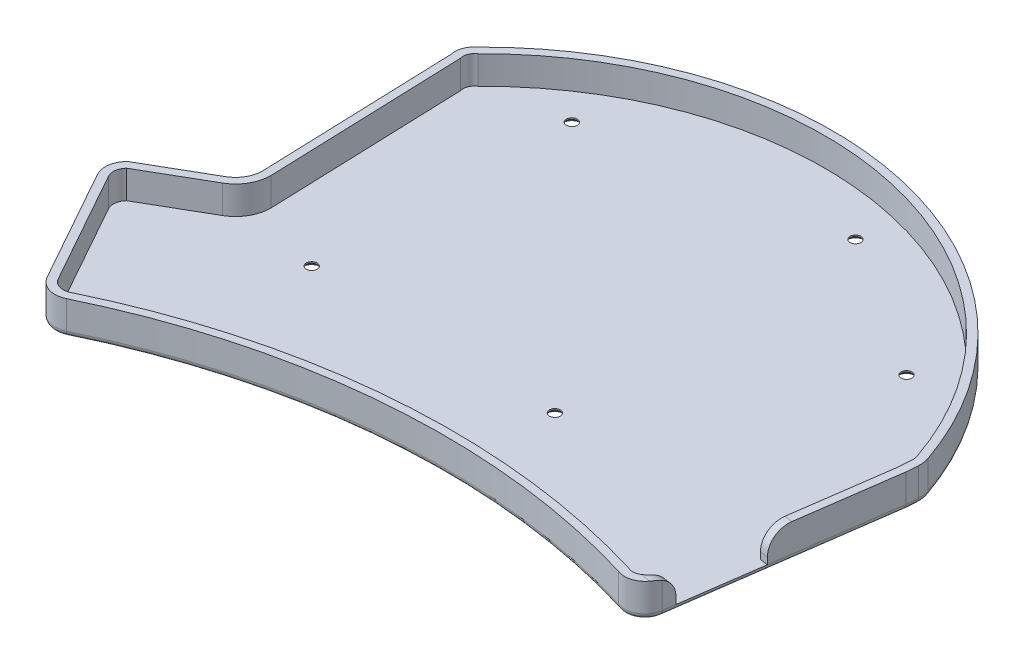
SolidWorks part; units mm, degrees
ref_plane "Front Plane" through (0, 0, 0) normal (0, 0, 1) x (1, 0, 0)
ref_plane "Top Plane" through (0, 0, 0) normal (0, 1, 0) x (1, 0, 0)
ref_plane "Right Plane" through (0, 0, 0) normal (1, 0, 0) x (0, 0, -1)
sketch "Sketch6" plane through (0, 1038.5381, 0) normal (0, 1, 0) x (1, 0, 0)
  line L0 (998.5428, -1001.8093) -> (999.7992, -1037.8748)
  line L1 (997.2992, -1042.205) -> (985.901, -1048.7857)
  line L2 (985.1163, -1053.683) -> (996.8887, -1074.7376)
  line L3 (1101.7127, -1066.0782) -> (1107.2534, -1026.654)
  line L4 (1107.2534, -1026.654) -> (1107.4097, -1024.4677)
  line L5 (1105.7609, -1026.4959) -> (1105.9135, -1024.3608)
  line L6 (1100.2273, -1065.8695) -> (1105.7609, -1026.4959)
  line L7 (986.4256, -1052.951) -> (998.198, -1074.0056)
  line L8 (998.0492, -1043.504) -> (986.8112, -1049.9922)
  line L9 (1000.0368, -1001.6089) -> (1001.2992, -1037.847)
  arc A0 (999.7992, -1037.8748) -> (997.2992, -1042.205) centre (994.7992, -1037.8748) cw
  arc A1 (985.901, -1048.7857) -> (985.1163, -1053.683) centre (988.6076, -1051.7309) ccw
  arc A2 (996.8887, -1074.7376) -> (1002.1244, -1076.3851) centre (1000.38, -1072.7855) ccw
  arc A3 (1002.1244, -1076.3851) -> (1096.6664, -1069.0373) centre (1058.765, -1193.2674) cw
  arc A4 (1096.6664, -1069.0373) -> (1101.7127, -1066.0782) centre (1098.0174, -1065.5589) ccw
  arc A5 (1107.4097, -1024.4677) -> (1107.1506, -1022.4849) centre (1102.4224, -1024.1112) ccw
  arc A6 (999.9792, -998.1245) -> (1107.1506, -1022.4849) centre (1046.0168, -1043.5119) cw
  circle A7 centre (1015.3354, -996.3599) radius 1
  circle A8 centre (1060.2451, -988.9185) radius 1
  circle A9 centre (1086.6166, -1005.8902) radius 1
  circle A10 centre (1060.2451, -1044.4029) radius 1
  circle A11 centre (1014.3354, -1043.3585) radius 1
  arc A12 (999.9792, -998.1245) -> (998.5428, -1001.8093) centre (1002.0712, -1001.0624) ccw
  arc A13 (1000.9439, -999.2828) -> (1105.7321, -1022.9728) centre (1046.0168, -1043.5119) cw
  arc A14 (1105.9135, -1024.3608) -> (1105.7321, -1022.9728) centre (1102.4224, -1024.1112) ccw
  arc A15 (1097.1645, -1067.621) -> (1100.2273, -1065.8695) centre (1098.0174, -1065.5589) ccw
  arc A16 (1001.4703, -1075.0353) -> (1097.1645, -1067.621) centre (1058.765, -1193.2674) cw
  arc A17 (998.198, -1074.0056) -> (1001.4703, -1075.0353) centre (1000.38, -1072.7855) ccw
  arc A18 (986.8112, -1049.9922) -> (986.4256, -1052.951) centre (988.6076, -1051.7309) ccw
  arc A19 (1001.2992, -1037.847) -> (998.0492, -1043.504) centre (994.7992, -1037.8748) cw
  arc A20 (1000.9439, -999.2828) -> (1000.0368, -1001.6089) centre (1002.0712, -1001.0624) ccw
  dimension "D1" = 1.5
extrude "Boss-Extrude1" add sketch "Sketch6" along normal blind 1 contours A13 A20 L9 A19 L8 A18 L7 A17 A16 A15 L6 L5 A14 A11 A10 A9 A8 A7 | A6 A12 L0 A0 L1 A1 L2 A2 A3 A4 L3 L4 A5 A20 A13 A14 L5 L6 A15 A16 A17 L7 A18 L8 A19 L9 region at (998.8573, 1038.5381, 999.8095) region at (1048.0165, 1038.5381, 1027.5532)
extrude "Boss-Extrude2" add sketch "Sketch6<5>" along normal blind 6.2 contours A6 A12 L0 A0 L1 A1 L2 A2 A3 A4 L3 L4 A5 A20 A13 A14 L5 L6 A15 A16 A17 L7 A18 L8 A19 L9 region at (998.8573, 1038.5381, 999.8095)
sketch "Sketch6<5>" plane through (0, 1038.5381, 0) normal (0, 1, 0) x (1, 0, 0) same geometry as "Sketch6"
fillet "Fillet2" radius 1 13 edges at (1107.3803, 1038.5381, 1023.4633) (1107.3316, 1038.5381, 1025.5609) (1099.905, 1038.5381, 1068.7778) (1104.483, 1038.5381, 1046.3661) (1048.7009, 1038.5381, 1063.7748) (999.1794, 1038.5381, 1076.6011) (991.0025, 1038.5381, 1064.2103) (984.658, 1038.5381, 1051.0981) (991.6001, 1038.5381, 1045.4953) (999.1293, 1038.5381, 1040.3748) (999.171, 1038.5381, 1019.8421) (1060.3462, 1038.5381, 980.4711) (998.7109, 1038.5381, 999.7525)
chamfer "Chamfer1" distance 0.75 angle 45 5 edges at (1060.2451, 1038.5381, 1045.4029) (1014.3354, 1038.5381, 1044.3585) (1015.3354, 1038.5381, 997.3599) (1060.2451, 1038.5381, 989.9185) (1086.6166, 1038.5381, 1006.8902)
sketch "Sketch7" plane through (0, 1044.7381, 0) normal (0, 1, 0) x (1, 0, 0)
  line L0 (1098.7581, -1063.347) -> (1104.5402, -1064.1596)
  line L1 (1098.7581, -1063.347) -> (1100.832, -1048.5906)
  line L2 (1104.5402, -1064.1596) -> (1106.6141, -1049.4032)
  line L3 (1100.832, -1048.5906) -> (1106.6141, -1049.4032)
extrude "Cut-Extrude1" cut sketch "Sketch7" against normal blind 5.2
fillet "Fillet3" radius 4 2 edges at (1101.2892, 1044.7381, 1063.7027) (1103.363, 1044.7381, 1048.9463)
